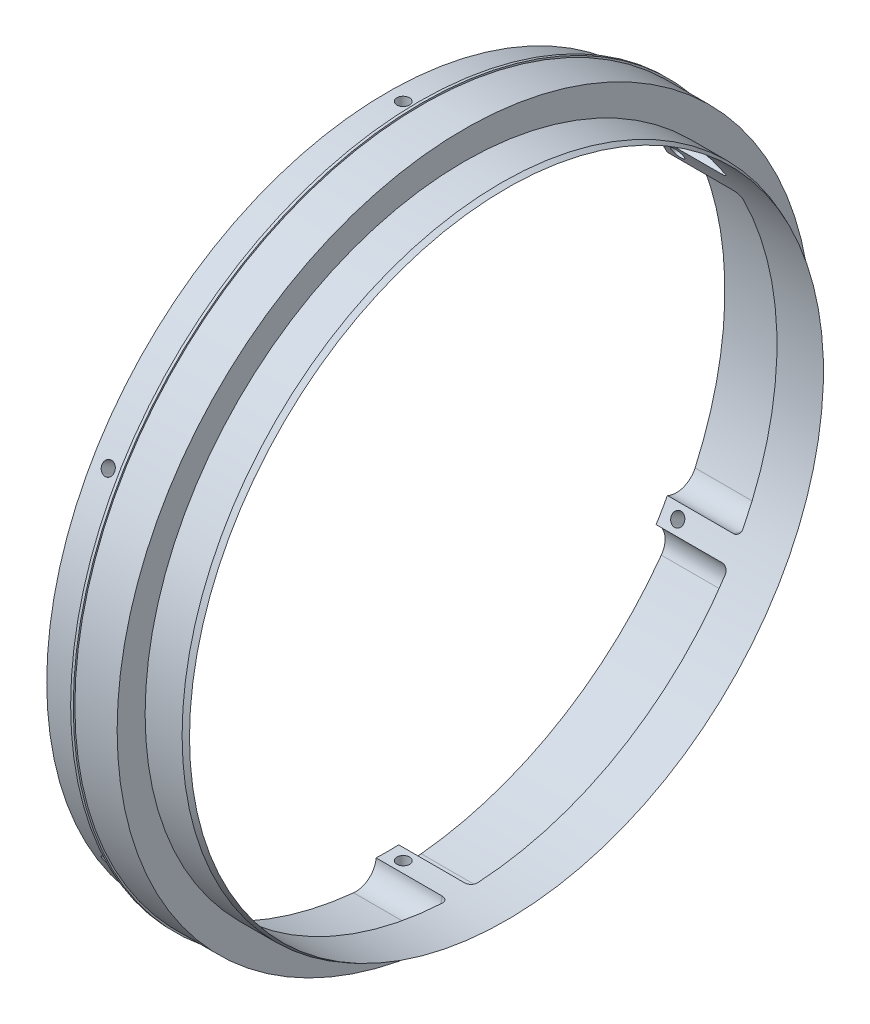
SolidWorks part; units mm, degrees
material "6061-T6 (SS)"
ref_plane "Front" through (0, 0, 0) normal (0, 0, 1) x (1, 0, 0)
ref_plane "Top" through (0, 0, 0) normal (0, 1, 0) x (1, 0, 0)
ref_plane "Right" through (0, 0, 0) normal (1, 0, 0) x (0, 0, -1)
sketch "Sketch1" plane through (0, 0, 0) normal (0, 0, 1) x (1, 0, 0)
  line L0 (-10.16, 0.508) -> (-1.27, 0.508)
  line L1 (-20.955, 7.62) -> (-20.32, 7.62)
  line L2 (-10.16, 7.239) -> (-10.16, 0.508)
  line L3 (0, 0) -> (-28.6258, 0)
  line L4 (-1.27, 0.508) -> (0, 0)
  line L5 (-28.6258, 5.6896) -> (-28.6258, 0)
  line L6 (-20.955, 7.62) -> (-20.955, 5.6896)
  line L7 (-20.955, 5.6896) -> (-28.6258, 5.6896)
  line L8 (-44.3099, -76.2) -> (29.4033, -76.2) construction
  line L9 (-20.32, 7.62) -> (-20.32, 7.239)
  line L10 (-20.32, 7.239) -> (-10.16, 7.239)
  dimension "D1" = 7.6708
  dimension "D2" = 0.508
  dimension "D3" = 0.635
  dimension "D4" = 10.16
  dimension "D5" = 76.2
  dimension "D6" = 5.6896
  dimension "D7" = 6.731
  dimension "D8" = 0.381
  dimension "D9" = 10.16
  dimension "D10" = 1.27
revolve "Revolve2" add sketch "Sketch1" angle 360 about L8
ref_point "Point1"
ref_plane "Plane1" through (0, -76.2, 0) normal (0, 1, 0) x (1, 0, 0)
ref_plane "Plane2" through (0, -158.0896, 0) normal (0, -1, 0) x (-1, 0, 0)
hole_wizard "#31 (0.12) Diameter Hole1" positions "3DSketch1" profile "Sketch11" hole size "#31" standard "ANSI Inch"
sketch3d "3DSketch1"
  point P0 (-24.8158, -158.0896, 0)
  dimension "D1" = 3.81
sketch "Sketch11" plane through (-24.8158, -158.0896, 0) normal (1, 0, 0) x (0, 0, -1)
  line L0 (0, 0) -> (0, 185.9821)
  line L1 (0, 185.9821) -> (1.524, 185.9821)
  line L2 (1.524, 185.9821) -> (1.524, 0)
  line L5 (1.524, 0) -> (0, 0)
  line L11 (0, -6.35) -> (0, 107.95) construction
  dimension "Thru Hole Dia." = 3.048
  dimension "Thru Hole Depth" = 185.9821
pattern_circular "CirPattern4" count 6 over 360 about axis through (-44.3099, -76.2, 0) along (-1, 0, 0) of "#31 (0.12) Diameter Hole1"
sketch "Sketch8" plane through (-28.6258, 0, 0) normal (-1, 0, 0) x (0, 0, 1)
  line L0 (-7.6343, -152.0166) -> (0, -76.2) construction
  line L1 (0, -76.2) -> (0, -152.4) construction
  line L2 (-61.8419, -120.7198) -> (0, -76.2) construction
  line L3 (0, -76.2) -> (-65.9911, -114.3) construction
  circle A0 centre (0, -76.2) radius 76.2 construction
  arc A1 (-65.841, -123.5988) -> (-8.128, -156.9194) centre (0, -76.2) ccw
  circle A2 centre (0, -76.2) radius 81.8896 construction
  circle A3 centre (0, -76.2) radius 76.2
  arc A4 (-64.5901, -116.6297) -> (-2.7181, -152.3515) centre (0, -76.2) ccw
  circle A5 centre (0, -76.2) radius 81.8896
  circle A6 centre (-61.8419, -120.7198) radius 4.9276
  circle A7 centre (-7.6343, -152.0166) radius 4.9276
  arc A8 (-1.524, -158.0754) -> (1.524, -158.0754) centre (0, -76.2) ccw construction
  arc A9 (-1.524, -152.3848) -> (1.524, -152.3848) centre (0, -76.2) ccw construction
  arc A10 (-1.524, -158.0754) -> (1.524, -158.0754) centre (0, -76.2) ccw
  arc A11 (-1.524, -152.3848) -> (1.524, -152.3848) centre (0, -76.2) ccw
  arc A12 (-64.5901, -116.6297) -> (-2.7181, -152.3515) centre (0, -76.2) ccw
  arc A13 (-66.7399, -112.9726) -> (-65.2159, -115.6122) centre (0, -76.2) ccw construction
  arc A14 (-66.7399, -112.9726) -> (-65.2159, -115.6122) centre (0, -76.2) ccw
  arc A15 (-71.6682, -115.8179) -> (-70.1442, -118.4575) centre (0, -76.2) ccw construction
  arc A16 (-71.6682, -115.8179) -> (-70.1442, -118.4575) centre (0, -76.2) ccw
  point P3 (0, -152.4)
  point P14 (-8.128, -156.9194)
  point P16 (-65.841, -123.5988)
  point P20 (-65.9911, -114.3)
  dimension "D2" = 5.75
  dimension "D3" = 0.762
  dimension "D4" = 5.75
  dimension "D1" = 0
extrude "Cut-Extrude1" cut sketch "Sketch8" against normal blind 17.4498
fillet "Fillet1" radius 1.5875 3 edges at (-11.176, -155.7816, -4.4553) (-11.176, -146.4586, -40.5638) (-11.176, -119.8492, -66.692)
pattern_circular "CirPattern3" count 6 over 360 about axis through (0, -76.2, 0) along (1, 0, 0) of "Cut-Extrude1", "Fillet1"
sketch3d "3DSketch2"
  circle A0 centre (-24.9799, -157.9493, -0.0042) radius 2.0193
  point P2 (-24.9799, -155.93, -0.0042)
  dimension "D1" = 4.0386
